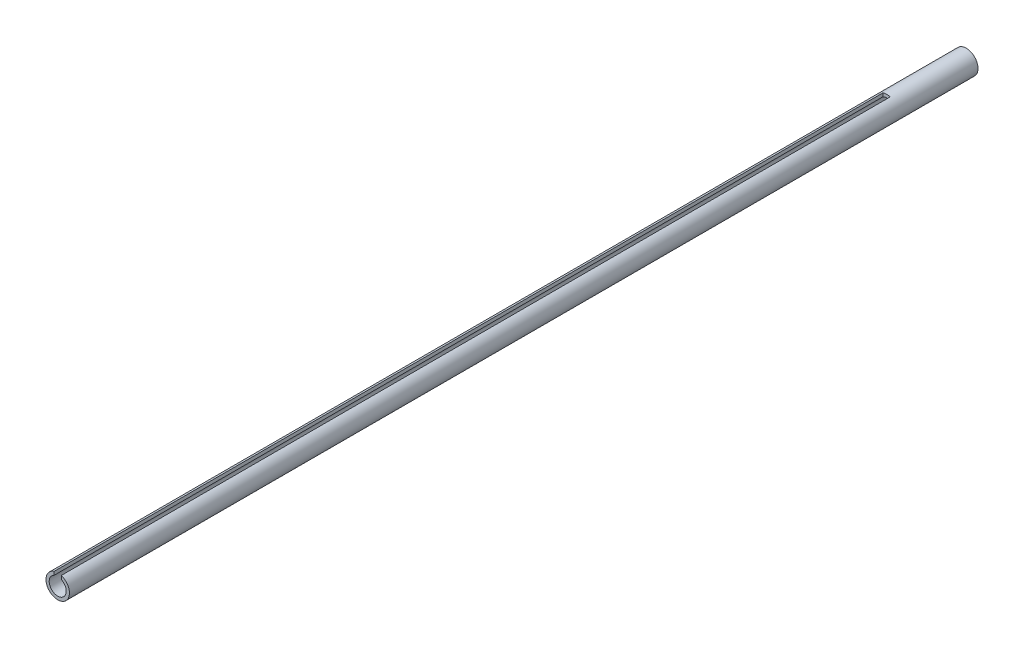
SolidWorks part; units mm, degrees
ref_plane "Front" through (0, 0, 0) normal (0, 0, 1) x (1, 0, 0)
ref_plane "Top" through (0, 0, 0) normal (0, 1, 0) x (1, 0, 0)
ref_plane "Right" through (0, 0, 0) normal (1, 0, 0) x (0, 0, -1)
sketch "Sketch1" plane through (0, 0, 0) normal (0, 0, 1) x (1, 0, 0)
  circle A0 centre (0, 0) radius 0.535
  circle A1 centre (0, 0) radius 0.735
  dimension "D1" = 1.07
  dimension "D2" = 1.47
extrude "Boss-Extrude1" add sketch "Sketch1" along normal blind 57
sketch "Sketch2" plane through (0, 0, 0) normal (0, 1, 0) x (1, 0, 0)
  line L0 (0, 0) -> (0, 2.224) construction
  line L1 (-0.225, -5) -> (0.225, -5)
  line L2 (-0.225, -5) -> (-0.225, -58)
  line L3 (-0.225, -58) -> (0.225, -58)
  line L4 (0.225, -5) -> (0.225, -58)
  line L5 (0.535, 0) -> (-0.535, 0) construction
  line L6 (-0.735, -57) -> (0.735, -57) construction
  dimension "D1" = 5
  dimension "D2" = 1
  dimension "D3" = 0.45
extrude "Cut-Extrude1" cut sketch "Sketch2" along normal through all
sketch "Sketch3" plane through (0, 0, 0) normal (0, 1, 0) x (1, 0, 0)
  line L0 (0, 0) -> (0, 2.8025) construction
  line L1 (-0.535, -57) -> (0.535, -57) construction
  line L2 (-0.5, -21) -> (0.5, -21)
  line L3 (-0.5, -21) -> (-0.5, -23)
  line L4 (-0.5, -23) -> (0.5, -23)
  line L5 (0.5, -21) -> (0.5, -23)
  dimension "D1" = 2
  dimension "D2" = 1
  dimension "D3" = 34
extrude "Cut-Extrude2" cut sketch "Sketch3" against normal through all
sketch "Sketch4" plane through (0, 0, 0) normal (0, 0, -1) x (-1, 0, 0)
  circle A0 centre (0, 0) radius 0.735 construction
  circle A1 centre (0, 0) radius 0.735
  circle A2 centre (0, 0) radius 0.535 construction
  circle A3 centre (0, 0) radius 0.535
ref_axis "Axis-Tube17" through (0, 0, 57) along (0, 0, -1)
